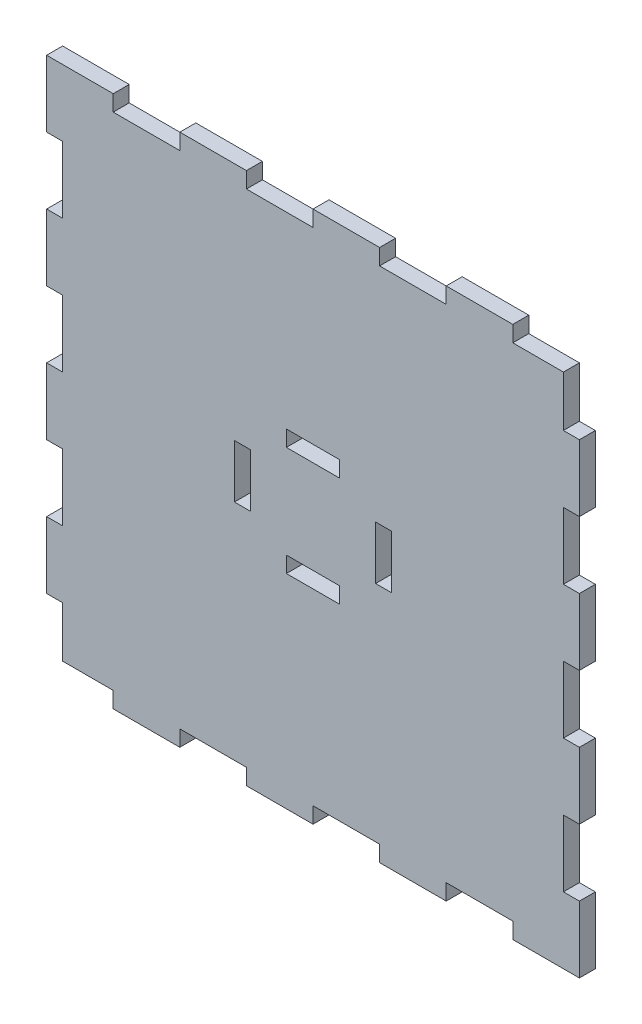
SolidWorks part; units mm, degrees
ref_plane "Plano frontal" through (0, 0, 0) normal (0, 0, 1) x (1, 0, 0)
ref_plane "Plano superior" through (0, 0, 0) normal (0, 1, 0) x (1, 0, 0)
ref_plane "Plano direito" through (0, 0, 0) normal (1, 0, 0) x (0, 0, -1)
sketch "Esboço1" plane through (0, 0, 0) normal (0, 0, 1) x (1, 0, 0)
  line L0 (200, 150) -> (200, 125)
  line L1 (0, 0) -> (200, 0)
  line L2 (0, 0) -> (0, 200)
  line L3 (0, 200) -> (200, 200)
  line L4 (200, 0) -> (200, 200)
  line L25 (200, 200) -> (194, 200)
  line L26 (200, 200) -> (200, 175)
  line L27 (200, 175) -> (194, 175)
  line L28 (194, 194) -> (194, 175)
  line L29 (200, 150) -> (194, 150)
  line L30 (194, 150) -> (194, 125)
  line L31 (200, 125) -> (194, 125)
  line L32 (200, 100) -> (200, 75)
  line L33 (200, 100) -> (194, 100)
  line L34 (194, 100) -> (194, 75)
  line L35 (200, 75) -> (194, 75)
  line L36 (200, 50) -> (200, 25)
  line L37 (200, 50) -> (194, 50)
  line L38 (194, 50) -> (194, 25)
  line L39 (200, 25) -> (194, 25)
  line L40 (0, 50) -> (0, 75)
  line L41 (0, 0) -> (6, 0)
  line L42 (0, 0) -> (0, 25)
  line L43 (0, 25) -> (6, 25)
  line L44 (6, 6) -> (6, 25)
  line L45 (0, 50) -> (6, 50)
  line L46 (6, 50) -> (6, 75)
  line L47 (0, 75) -> (6, 75)
  line L48 (0, 100) -> (0, 125)
  line L49 (0, 100) -> (6, 100)
  line L50 (6, 100) -> (6, 125)
  line L51 (0, 125) -> (6, 125)
  line L52 (0, 150) -> (0, 175)
  line L53 (0, 150) -> (6, 150)
  line L54 (6, 150) -> (6, 175)
  line L55 (0, 175) -> (6, 175)
  line L56 (50, 0) -> (50, 6)
  line L57 (0, 0) -> (25, 0)
  line L58 (0, 0) -> (0, 6)
  line L59 (6, 6) -> (25, 6)
  line L60 (25, 0) -> (25, 6)
  line L61 (50, 0) -> (75, 0)
  line L62 (75, 0) -> (75, 6)
  line L63 (50, 6) -> (75, 6)
  line L64 (100, 0) -> (100, 6)
  line L65 (100, 0) -> (125, 0)
  line L66 (125, 0) -> (125, 6)
  line L67 (100, 6) -> (125, 6)
  line L68 (150, 0) -> (150, 6)
  line L69 (150, 0) -> (175, 0)
  line L70 (175, 0) -> (175, 6)
  line L71 (150, 6) -> (175, 6)
  line L72 (150, 200) -> (150, 194)
  line L73 (200, 200) -> (175, 200)
  line L74 (200, 200) -> (200, 194)
  line L75 (194, 194) -> (175, 194)
  line L76 (175, 200) -> (175, 194)
  line L77 (150, 200) -> (125, 200)
  line L78 (125, 200) -> (125, 194)
  line L79 (150, 194) -> (125, 194)
  line L80 (100, 200) -> (100, 194)
  line L81 (100, 200) -> (75, 200)
  line L82 (75, 200) -> (75, 194)
  line L83 (100, 194) -> (75, 194)
  line L84 (50, 200) -> (50, 194)
  line L85 (50, 200) -> (25, 200)
  line L86 (25, 200) -> (25, 194)
  line L87 (50, 194) -> (25, 194)
  line L120 (76.5, 110) -> (123.5, 110) construction
  line L121 (76.5, 110) -> (70.5, 110)
  line L123 (56.4741, 200) -> (56.4741, 110) construction
  line L136 (0, 110) -> (76.5, 110) construction
  line L186 (76.5, 110) -> (76.5, 90)
  line L195 (76.5, 90) -> (70.5, 90)
  line L196 (70.5, 110) -> (70.5, 90)
  line L197 (0, 100) -> (200, 100) construction
  line L198 (123.5, 110) -> (129.5, 110)
  line L199 (123.5, 110) -> (123.5, 90)
  line L200 (123.5, 90) -> (129.5, 90)
  line L201 (129.5, 110) -> (129.5, 90)
  line L202 (100, 0) -> (100, 117.5) construction
  line L203 (100, 100) -> (100, 117.5) construction
  line L204 (100, 123.5) -> (100, 200) construction
  line L205 (100, 117.5) -> (110, 117.5)
  line L207 (100, 123.5) -> (110, 123.5)
  line L208 (110, 117.5) -> (110, 123.5)
  line L209 (100, 123.5) -> (90, 123.5)
  line L211 (100, 117.5) -> (90, 117.5)
  line L212 (90, 123.5) -> (90, 117.5)
  line L213 (90, 76.5) -> (90, 82.5)
  line L214 (100, 82.5) -> (90, 82.5)
  line L215 (100, 76.5) -> (90, 76.5)
  line L216 (110, 82.5) -> (110, 76.5)
  line L217 (100, 76.5) -> (110, 76.5)
  line L218 (100, 82.5) -> (110, 82.5)
  dimension "D1" = 200
  dimension "D3" = 90
  dimension "D4" = 20
  dimension "D5" = 6
  dimension "D6" = 47
  dimension "D7" = 6
  dimension "D8" = 17.5
  dimension "D9" = 6
  dimension "D10" = 25
  dimension "D11" = 6
  dimension "D13" = 25
  dimension "D14" = 6
  dimension "D16" = 6
  dimension "D17" = 25
  dimension "D19" = 6
  dimension "D20" = 25
  dimension "D22" = 10
  dimension "D23" = 10
  dimension "D12" = 4
  dimension "D15" = 4
  dimension "D18" = 4
  dimension "D21" = 4
extrude "Ressalto-extrusão1" add sketch "Esboço1" along normal blind 6 contours L50 L136 L123 L3 L84 L87 L86 L2 L55 L54 L53 L51 region at (100, 100, 0)
